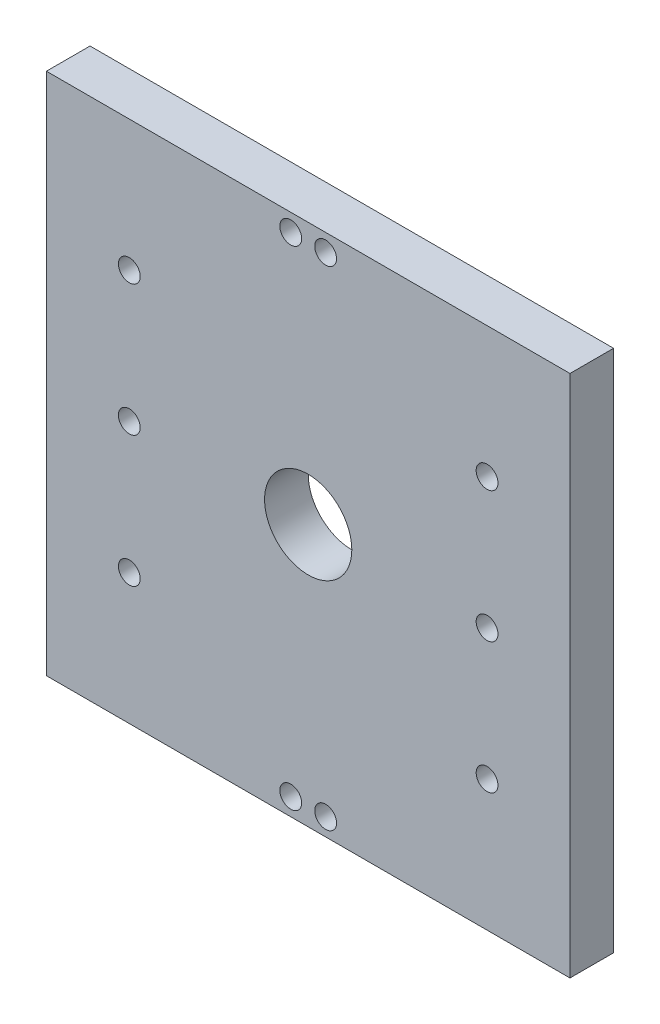
SolidWorks part; units mm, degrees
ref_plane "Front Plane" through (0, 0, 0) normal (0, 0, 1) x (1, 0, 0)
ref_plane "Top Plane" through (0, 0, 0) normal (0, 1, 0) x (1, 0, 0)
ref_plane "Right Plane" through (0, 0, 0) normal (1, 0, 0) x (0, 0, -1)
sketch "Sketch1" plane through (0, 0, 0) normal (0, 1, 0) x (1, 0, 0)
  line L1 (-60, -5) -> (60, -5)
  line L2 (-60, -5) -> (-60, 5)
  line L3 (-60, 5) -> (60, 5)
  line L4 (60, -5) -> (60, 5)
  line L5 (-60, -5) -> (60, 5) construction
  line L6 (-60, 5) -> (60, -5) construction
  point P0 (0, 0)
  dimension "D1" = 120
  dimension "D2" = 10
extrude "Boss-Extrude1" add sketch "Sketch1" along normal blind 120
sketch "Sketch2" plane through (0, 0, 5) normal (0, 0, 1) x (1, 0, 0)
  line L0 (60, 120) -> (-60, 120) construction
  line L1 (60, 0) -> (-60, 0) construction
  circle A0 centre (0, 60) radius 10
  circle A1 centre (-41, 60) radius 2.5
  circle A2 centre (-41, 30) radius 2.5
  circle A3 centre (-41, 90) radius 2.5
  circle A4 centre (41, 60) radius 2.5
  circle A5 centre (41, 30) radius 2.5
  circle A6 centre (41, 90) radius 2.5
  circle A7 centre (-4, 116) radius 2.5
  circle A8 centre (4, 116) radius 2.5
  circle A9 centre (-4, 4) radius 2.5
  circle A10 centre (4, 4) radius 2.5
  point P0 (0, 0)
  point P1 (0, 60)
  point P30 (0, 0)
  dimension "D3" = 41
  dimension "D4" = 30
  dimension "D9" = 4
  dimension "D14" = 4
  dimension "D15" = 8
  dimension "D1" = 60
  dimension "D2" = 60
  dimension "D5" = 30
  dimension "D6" = 41
  dimension "D7" = 30
  dimension "D8" = 30
  dimension "D10" = 4
  dimension "D11" = 4
  dimension "D12" = 0
  dimension "D13" = 0
extrude "Cut-Extrude1" cut sketch "Sketch2" against normal up to surface (10 mm away) up to face at (0, 60, -5)
